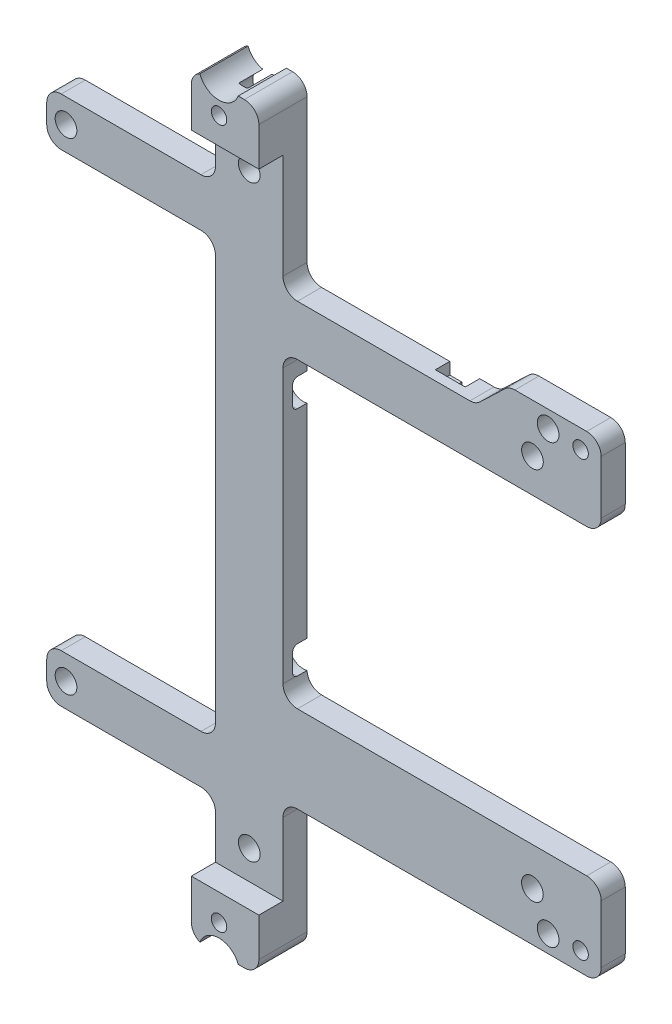
SolidWorks part; units mm, degrees
ref_plane "Front Plane" through (0, 0, 0) normal (1, 0, 0) x (0, 1, 0)
ref_plane "Top Plane" through (0, 0, 0) normal (0, 0, 1) x (0, 1, 0)
ref_plane "Right Plane" through (0, 0, 0) normal (0, 1, 0) x (-1, 0, 0)
sketch "Sketch1" plane through (0, 0, 0) normal (0, 0, 1) x (0, 1, 0)
  line L0 (-38.86, 0.005) -> (38.86, -0.005) construction
  line L1 (-38.86, 0.005) -> (38.86, -0.005) construction
  line L2 (0, 0) -> (0, 106.5364) construction
  line L13 (-67.5, 65.745) -> (67.5, 51.745) construction
  line L14 (-67.5, 51.745) -> (67.5, 65.745) construction
  line L17 (-45, 65.745) -> (45, 65.745)
  line L22 (62.0223, 59.9423) -> (59.9389, 57.5466) construction
  line L23 (62.1784, 57.7039) -> (59.7816, 59.7861) construction
  line L45 (42.2651, 11.7705) -> (42.2651, 52.7631) construction
  line L47 (-48.9476, 51.745) -> (-48.9476, -14.255)
  line L48 (-48.9476, -14.255) -> (-30.9476, -14.255)
  line L49 (-30.9476, -14.255) -> (-30.9476, 51.745)
  line L50 (-30.9476, 51.745) -> (31.792, 51.745)
  line L51 (31.792, 51.745) -> (31.792, -14.255)
  line L52 (31.792, -14.255) -> (48.8866, -14.255)
  line L53 (48.8866, -14.255) -> (48.8866, 4.8443)
  line L54 (48.8866, 4.8443) -> (42.2651, 11.7705)
  line L55 (42.2651, 11.7705) -> (42.2651, 51.745)
  line L60 (-55, 65.745) -> (-78, 65.745)
  line L62 (-78, 65.745) -> (-78, 51.745)
  line L63 (-78, 51.745) -> (-48.9476, 51.745)
  line L64 (78, 65.745) -> (78, 51.745)
  line L65 (55, 65.745) -> (78, 65.745)
  line L66 (78, 51.745) -> (42.2651, 51.745)
  line L67 (-55, 65.745) -> (-55, 100.745)
  line L68 (-55, 100.745) -> (-45, 100.745)
  line L69 (-45, 100.745) -> (-45, 65.745)
  line L70 (45, 100.745) -> (45, 65.745)
  line L71 (55, 100.745) -> (45, 100.745)
  line L72 (55, 65.745) -> (55, 100.745)
  circle A0 centre (-38.86, 0.005) radius 2.25
  circle A1 centre (38.86, -0.005) radius 2.25
  circle A2 centre (-60.99, 58.735) radius 2.25
  circle A3 centre (60.98, 58.745) radius 2.25
  circle A8 centre (-45, -9.995) radius 1.6
  circle A10 centre (45, -9.995) radius 1.6
  circle A14 centre (60.98, 58.745) radius 1.5874 construction
  circle A15 centre (-72.5, 60.005) radius 3
  circle A17 centre (72.5, 60.005) radius 3
  point P25 (-54.1614, 65.745)
  point P28 (0, 58.745)
  dimension "D1" = 4.5
  dimension "D4" = 4.5
  dimension "D5" = 4.5
  dimension "D10" = 4.5
  dimension "D11" = 3.2
  dimension "D13" = 45
  dimension "D12" = 10
  dimension "D14" = 6
  dimension "D16" = 70
  dimension "D2" = 77.72
  dimension "D3" = 0.01
  dimension "D6" = 22.13
  dimension "D7" = 58.73
  dimension "D8" = 99.84
  dimension "D9" = 58.74
  dimension "D15" = 72.5
  dimension "D17" = 14
  dimension "D18" = 23
  dimension "D19" = 10
  dimension "D20" = 35
  dimension "D22" = 66
  dimension "D23" = 18
  dimension "D24" = 62.7397
extrude "Boss-Extrude1" add sketch "Sketch1" along normal blind 5
sketch "Sketch4" plane through (0, 0, 5) normal (0, 0, 1) x (1, 0, 0)
  line L0 (-59.9423, 62.0223) -> (-57.5466, 59.9389) construction
  line L1 (-57.7039, 62.1784) -> (-59.7861, 59.7816) construction
  line L2 (-52.7631, 68.2675) -> (-66.1639, 68.2675) construction
  line L3 (-66.1639, 68.2675) -> (-66.1639, 50.4408) construction
  line L4 (-66.1639, 50.4408) -> (-106.6121, 50.4408) construction
  line L5 (-106.6121, 50.4408) -> (-106.6121, 34.0894) construction
  line L6 (-106.6121, 34.0894) -> (-66.1639, 34.0894) construction
  line L7 (-66.1639, 34.0894) -> (-66.1639, -39.7992) construction
  line L8 (-66.1639, -39.7992) -> (-105.8744, -39.7992) construction
  line L9 (-105.8744, -39.7992) -> (-105.8744, -55.1671) construction
  line L10 (-105.8744, -55.1671) -> (-65.4262, -55.1671) construction
  line L11 (-65.4262, -55.1671) -> (-65.4262, -83.2031) construction
  line L12 (-65.4262, -83.2031) -> (-51.2429, -83.2031) construction
  line L13 (-51.2429, -83.2031) -> (-51.2429, -48.9476) construction
  line L14 (-51.2429, -48.9476) -> (16.9144, -48.9476) construction
  line L15 (16.9144, -48.9476) -> (16.9144, -14.8647) construction
  line L16 (16.9144, -14.8647) -> (-49.6702, -14.8647) construction
  line L17 (-49.6702, -14.8647) -> (-49.6702, 30.0022) construction
  line L18 (-49.6702, 30.0022) -> (-49.6702, 31.792) construction
  line L19 (-49.6702, 31.792) -> (21.8605, 31.792) construction
  line L20 (21.8605, 31.792) -> (21.8605, 50.4408) construction
  line L21 (21.8605, 50.4408) -> (-3.2186, 50.4408) construction
  line L22 (-3.2186, 50.4408) -> (-11.7705, 42.2651) construction
  line L23 (-11.7705, 42.2651) -> (-52.7631, 42.2651) construction
  line L24 (-52.7631, 42.2651) -> (-52.7631, 68.2675) construction
  line L25 (-53.5293, 13.6559) -> (-53.5293, 8.5989) construction
  line L26 (-53.5293, 13.6559) -> (-57.5472, 13.6559) construction
  line L27 (-57.5472, 13.6559) -> (-57.5472, 8.5989) construction
  line L28 (-53.5293, 8.5989) -> (-57.5472, 8.5989) construction
  line L29 (-53.5293, 13.6559) -> (-57.5472, 8.5989) construction
  line L30 (-57.5472, 13.6559) -> (-53.5293, 8.5989) construction
  line L31 (-30.5241, 33.1453) -> (-30.5241, 30.4388) construction
  line L32 (-30.5241, 33.1453) -> (-34.3522, 33.1453) construction
  line L33 (-34.3522, 33.1453) -> (-34.3522, 30.4388) construction
  line L34 (-30.5241, 30.4388) -> (-34.3522, 30.4388) construction
  line L35 (-30.5241, 33.1453) -> (-34.3522, 30.4388) construction
  line L36 (-34.3522, 33.1453) -> (-30.5241, 30.4388) construction
  line L37 (-34.5262, 33.1453) -> (-34.5262, 30.4388) construction
  line L38 (-34.5262, 33.1453) -> (-37.7452, 33.1453) construction
  line L39 (-37.7452, 33.1453) -> (-37.7452, 30.4388) construction
  line L40 (-34.5262, 30.4388) -> (-37.7452, 30.4388) construction
  line L41 (-34.5262, 33.1453) -> (-37.7452, 30.4388) construction
  line L42 (-37.7452, 33.1453) -> (-34.5262, 30.4388) construction
  line L43 (-16.3911, 40.3217) -> (-16.3911, 37.7641) construction
  line L44 (-16.3911, 40.3217) -> (-19.6245, 40.3217) construction
  line L45 (-19.6245, 40.3217) -> (-19.6245, 37.7641) construction
  line L46 (-16.3911, 37.7641) -> (-19.6245, 37.7641) construction
  line L47 (-16.3911, 40.3217) -> (-19.6245, 37.7641) construction
  line L48 (-19.6245, 40.3217) -> (-16.3911, 37.7641) construction
  line L49 (-15.9373, 44.8094) -> (-15.9373, 40.9494) construction
  line L50 (-15.9373, 44.8094) -> (-22.1441, 44.8094) construction
  line L51 (-22.1441, 44.8094) -> (-22.1441, 40.9494) construction
  line L52 (-15.9373, 40.9494) -> (-22.1441, 40.9494) construction
  line L53 (-15.9373, 44.8094) -> (-22.1441, 40.9494) construction
  line L54 (-22.1441, 44.8094) -> (-15.9373, 40.9494) construction
  circle A0 centre (-58.745, 60.98) radius 1.5874 construction
  circle A1 centre (-52.5383, 22.8611) radius 3 construction
  circle A2 centre (-52.5383, -25.1544) radius 3 construction
  circle A3 centre (-10.615, -39.3884) radius 1 construction
  circle A4 centre (-10.615, -46.9884) radius 1 construction
  circle A5 centre (-19.6245, -25.1544) radius 3 construction
  circle A6 centre (-58.745, 60.98) radius 2.25 construction
  point P33 (-55.5383, 11.1274)
  point P44 (-32.4381, 31.792)
  point P49 (-36.1357, 31.792)
  point P54 (-18.0078, 39.0429)
  point P59 (-19.0407, 42.8794)
sketch "Sketch5" plane through (0, 0, 0) normal (0, 0, -1) x (1, 0, 0)
  line L0 (-16.3911, -39.8089) -> (-15.9373, -39.8089)
  line L1 (-57.5472, -8.5989) -> (-53.5293, -8.5989)
  line L2 (-57.5472, -8.5989) -> (-57.5472, -13.6559)
  line L3 (-57.5472, -13.6559) -> (-53.5293, -13.6559)
  line L4 (-53.5293, -8.5989) -> (-53.5293, -13.6559)
  line L5 (-57.5472, -8.5989) -> (-53.5293, -13.6559) construction
  line L6 (-57.5472, -13.6559) -> (-53.5293, -8.5989) construction
  line L7 (-37.7452, -30.4388) -> (-30.5241, -30.4388)
  line L8 (-37.7452, -30.4388) -> (-37.7452, -33.1453)
  line L9 (-37.7452, -33.1453) -> (-30.5241, -33.1453)
  line L10 (-30.5241, -30.4388) -> (-30.5241, -33.1453)
  line L11 (-19.6245, -37.7641) -> (-16.3911, -37.7641)
  line L12 (-19.6245, -37.7641) -> (-19.6245, -39.8089)
  line L14 (-16.3911, -37.7641) -> (-16.3911, -39.8089)
  line L15 (-22.1441, -39.8089) -> (-19.6245, -39.8089)
  line L16 (-22.1441, -39.8089) -> (-22.1441, -44.8094)
  line L17 (-22.1441, -44.8094) -> (-15.9373, -44.8094)
  line L18 (-15.9373, -39.8089) -> (-15.9373, -44.8094)
  circle A0 centre (-52.5383, -22.8611) radius 3
  circle A1 centre (-52.5383, 25.1544) radius 3
  circle A2 centre (-10.615, 46.9884) radius 1
  circle A3 centre (-10.615, 39.3884) radius 1
  point P6 (-55.5383, -11.1274)
extrude "Cut-Extrude1" cut sketch "Sketch5" against normal blind 3
sketch "Sketch7" plane through (0, 0, 5) normal (0, 0, 1) x (1, 0, 0)
  line L0 (-51.745, 42.2651) -> (-51.745, 78) construction
  line L1 (-65.745, 78) -> (-51.745, 78)
  line L2 (-65.745, 78) -> (-65.745, 67)
  line L3 (-65.745, 67) -> (-51.745, 67)
  line L4 (-51.745, 78) -> (-51.745, 67)
  line L5 (0, 0) -> (-129.6565, 0) construction
  line L6 (-51.745, -78) -> (-51.745, -67)
  line L7 (-65.745, -67) -> (-51.745, -67)
  line L8 (-65.745, -78) -> (-65.745, -67)
  line L9 (-65.745, -78) -> (-51.745, -78)
  dimension "D1" = 11
extrude "Boss-Extrude2" add sketch "Sketch7" along normal blind 5
sketch "Sketch8" plane through (0, 0, 10) normal (0, 0, 1) x (1, 0, 0)
  line L0 (0, 0) -> (-41.2457, 0) construction
  circle A0 centre (-60.005, 72.5) radius 1.6
  circle A1 centre (-60.005, -72.5) radius 1.6
  dimension "D1" = 3.2
extrude "Cut-Extrude2" cut sketch "Sketch8" against normal blind 10
fillet "Fillet2" radius 1 15 edges at (-11.615, -46.9884, 3) (-11.615, -39.3884, 3) (-18.0078, 37.7641, 3) (-16.3911, 38.7865, 3) (-19.6245, 38.7865, 3) (-20.8843, 39.8089, 3) (-30.5241, 32.4687, 3) (-37.7452, 32.4687, 3) (-34.1347, 33.1453, 3) (-55.5383, 22.8611, 3) (-55.5383, -25.1544, 3) (-55.5383, 8.5989, 3) (-53.5293, 11.1274, 3) (-55.5383, 13.6559, 3) (-57.5472, 11.1274, 3)
sketch "Sketch9" plane through (0, 0, 10) normal (0, 0, 1) x (1, 0, 0)
  line L0 (0, 0) -> (-47.8889, 0) construction
  circle A0 centre (-60.005, 79.5) radius 4.25
  circle A2 centre (-60.005, -79.5) radius 4.25
extrude "Cut-Extrude3" cut sketch "Sketch9" against normal blind 10
sketch "Sketch10" plane through (0, 0, 0) normal (0, 0, -1) x (1, 0, 0)
  circle A0 centre (9.995, 45) radius 3
  circle A1 centre (9.995, -45) radius 3
  dimension "D1" = 6
  dimension "D2" = 6
extrude "Cut-Extrude4" cut sketch "Sketch10" against normal blind 2
fillet "Fillet1" radius 3 22 edges at (-51.745, -78, 5) (-65.745, -78, 5) (-65.745, -55, 2.5) (-100.745, -55, 2.5) (-100.745, -45, 2.5) (-65.745, -45, 2.5) (-65.745, 45, 2.5) (-100.745, 45, 2.5) (-100.745, 55, 2.5) (-65.745, 55, 2.5) (-65.745, 78, 5) (-51.745, 78, 5) (-51.745, 42.2651, 2.5) (-11.7705, 42.2651, 2.5) (-4.8443, 48.8866, 2.5) (14.255, 48.8866, 2.5) (14.255, 31.792, 2.5) (-51.745, 31.792, 2.5) (-51.745, -30.9476, 2.5) (14.255, -30.9476, 2.5) (14.255, -48.9476, 2.5) (-51.745, -48.9476, 2.5)
sketch "Sketch11" plane through (0, 0, 5) normal (0, 0, 1) x (1, 0, 0)
  line L0 (-68.745, -45) -> (-97.745, -45) construction
  line L1 (-100.745, -48) -> (-100.745, -52) construction
  line L2 (0, 0) -> (-111.0274, 0) construction
  line L3 (-48.745, -48.9476) -> (11.255, -48.9476) construction
  line L4 (14.255, -45.9476) -> (14.255, -33.9476) construction
  circle A0 centre (-96.745, -50) radius 2.25
  circle A1 centre (-96.745, 50) radius 2.25
  circle A2 centre (3.255, -45.3476) radius 2.25
  circle A5 centre (3.255, 45.3476) radius 2.25
  dimension "D1" = 4.5
  dimension "D4" = 4.5
  dimension "D2" = 5
  dimension "D3" = 4
  dimension "D5" = 3.6
  dimension "D6" = 11
extrude "Cut-Extrude5" cut sketch "Sketch11" against normal blind 10
